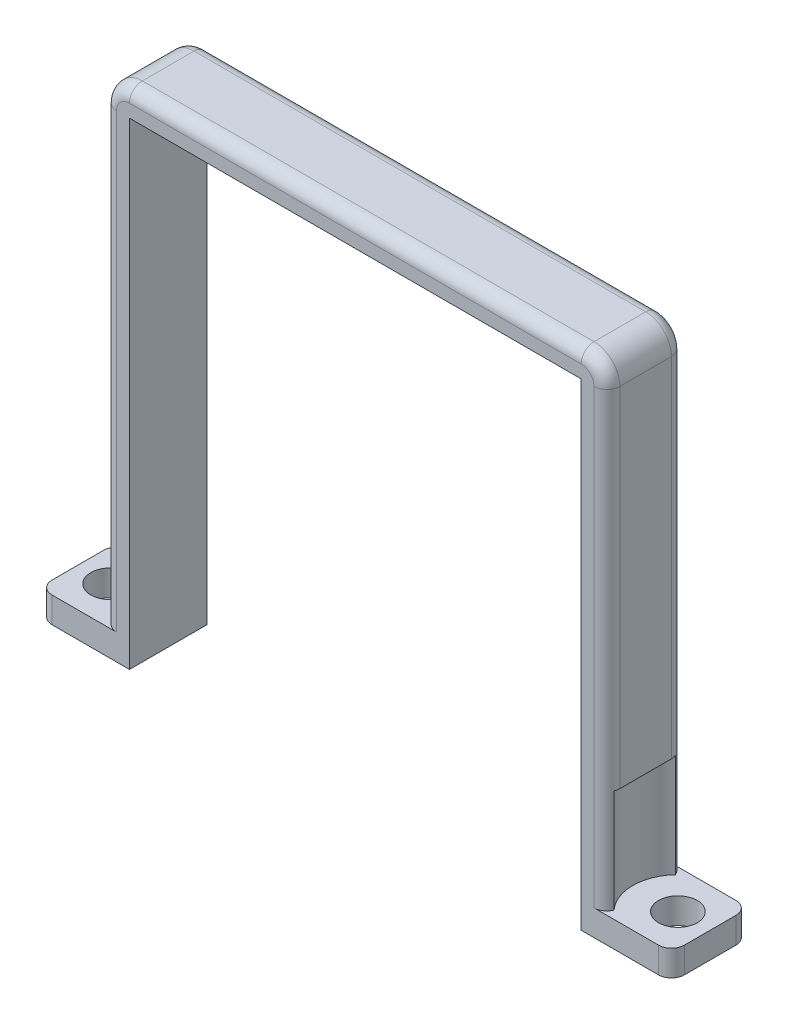
SolidWorks part; units mm, degrees
material "ABS"
ref_plane "Front Plane" through (0, 0, 0) normal (0, 0, 1) x (1, 0, 0)
ref_plane "Top Plane" through (0, 0, 0) normal (0, 1, 0) x (1, 0, 0)
ref_plane "Right Plane" through (0, 0, 0) normal (1, 0, 0) x (0, 0, -1)
sketch "Sketch1" plane through (0, 0, 0) normal (0, 0, 1) x (1, 0, 0)
  line L0 (-24.5, 0) -> (-17.5, 0)
  line L1 (-17.5, 0) -> (-17.5, 37)
  line L2 (-17.5, 37) -> (17.5, 37)
  line L3 (0, 37) -> (0, 39)
  line L4 (19.5, 39) -> (-19.5, 39)
  line L5 (-19.5, 39) -> (-19.5, 2)
  line L6 (-19.5, 2) -> (-24.5, 2)
  line L7 (-24.5, 2) -> (-24.5, 0)
  line L8 (24.5, 2) -> (24.5, 0)
  line L9 (19.5, 2) -> (24.5, 2)
  line L10 (19.5, 39) -> (19.5, 2)
  line L11 (17.5, 0) -> (17.5, 37)
  line L12 (24.5, 0) -> (17.5, 0)
  dimension "D1" = 2
  dimension "D2" = 2
  dimension "D3" = 2
  dimension "D4" = 5
  dimension "D5" = 35
  dimension "D6" = 37
extrude "Boss-Extrude1" add sketch "Sketch1" along normal blind 6 contours L6 L7 L0 L1 L2 L3 L4 L5 | L12 L8 L9 L10 L4 L3 L2 L11 region at (-24.0394, 1, 0) region at (0.4606, 38, 0)
sketch "Sketch2" plane through (0, 2, 0) normal (0, 1, 0) x (1, 0, 0)
  line L0 (0, 0) -> (0, -6) construction
  line L1 (19.5, 0) -> (-19.5, 0) construction
  line L2 (19.5, -6) -> (-19.5, -6) construction
  line L3 (-19.5, 0) -> (-24.5, 0) construction
  circle A0 centre (-22, -3) radius 1.5
  circle A1 centre (22, -3) radius 1.5
  point P2 (0, -3)
  point P11 (-22, 0)
  dimension "D1" = 3
extrude "Cut-Extrude1" cut sketch "Sketch2" against normal up to surface (2 mm away) up to face at (21, 0, 3)
fillet "Fillet1" radius 2 2 edges at (-19.5, 39, 3) (19.5, 39, 3)
sketch "Sketch3" plane through (0, 2, 0) normal (0, 1, 0) x (1, 0, 0)
  line L0 (0, 0) -> (0, -6) construction
  line L1 (17.5, -6) -> (-17.5, -6) construction
  circle A0 centre (-22, -3) radius 3.5
  circle A1 centre (22, -3) radius 3.5
  dimension "D1" = 7
extrude "Cut-Extrude2" cut sketch "Sketch3" along normal blind 8
fillet "Fillet2" radius 1 14 edges at (19.5, 19.5, 0) (18.9142, 38.4142, 0) (0, 39, 0) (-18.9142, 38.4142, 0) (19.5, 19.5, 6) (18.9142, 38.4142, 6) (0, 39, 6) (-18.9142, 38.4142, 6) (-19.5, 19.5, 0) (-19.5, 19.5, 6) (24.5, 1, 0) (24.5, 1, 6) (-24.5, 1, 0) (-24.5, 1, 6)
